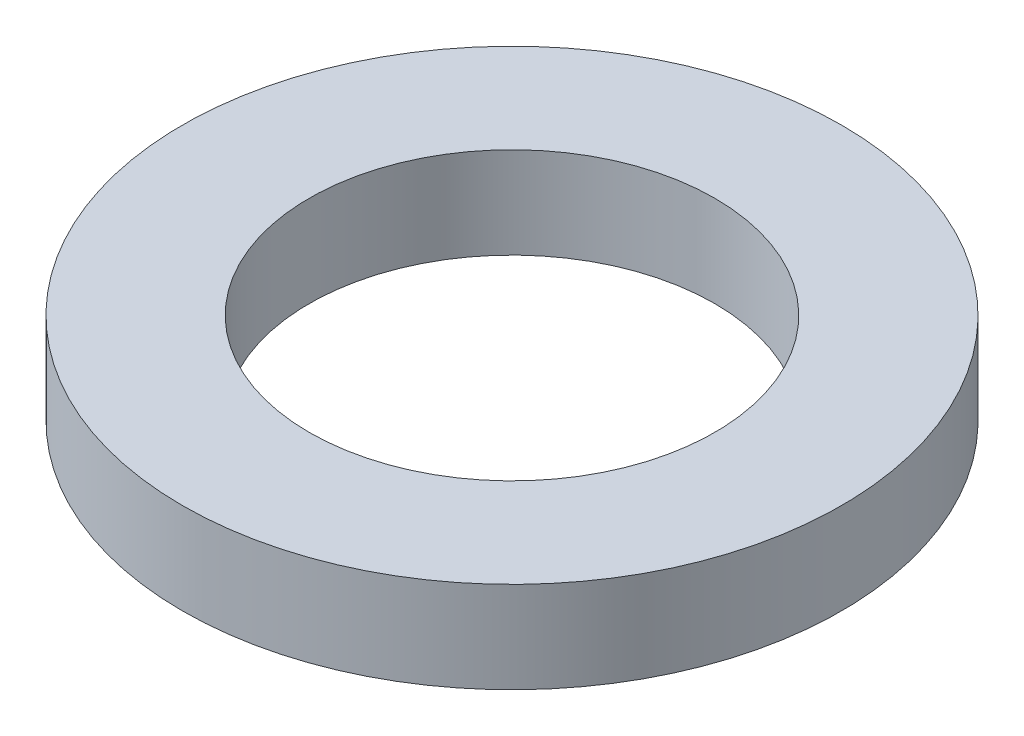
SolidWorks part; units mm, degrees
ref_plane "Front Plane" through (0, 0, 0) normal (0, 0, 1) x (1, 0, 0)
ref_plane "Top Plane" through (0, 0, 0) normal (0, 1, 0) x (1, 0, 0)
ref_plane "Right Plane" through (0, 0, 0) normal (1, 0, 0) x (0, 0, -1)
sketch "Sketch1" plane through (0, 0, 0) normal (0, 1, 0) x (1, 0, 0)
  circle A0 centre (0, 0) radius 65
  dimension "FLANGE_OD" = 130
extrude "Boss-Extrude1" add sketch "Sketch1" along normal blind 18
sketch "Sketch2" plane through (0, 0, 0) normal (0, 1, 0) x (1, 0, 0)
  circle A0 centre (0, 0) radius 40
  dimension "BORE_D" = 80
extrude "Cut-Extrude1" cut sketch "Sketch2" along normal through all
sketch "Sketch3" plane through (0, 18, 0) normal (0, 1, 0) x (1, 0, 0)
  circle A0 centre (0, 0) radius 28.5244 construction
  circle A1 centre (-28.5244, 0) radius 3.2773
  dimension "BOLT_D" = 6.5547
  dimension "BOLT_PCD" = 57.0487
extrude "Cut-Extrude2" cut sketch "Sketch3" against normal blind 15.4204 rebuild error yes
pattern_circular "CirPattern1" count 3 over 360 rebuild error yes
